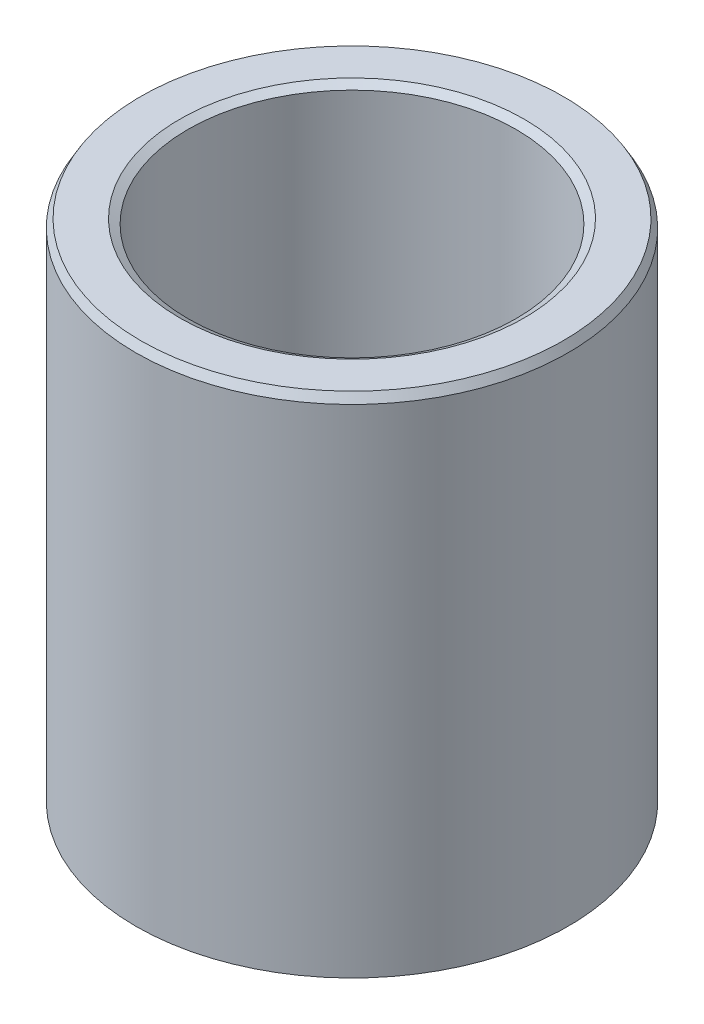
SolidWorks part; units mm, degrees
ref_plane "Front Plane" through (0, 0, 0) normal (0, 0, 1) x (1, 0, 0)
ref_plane "Top Plane" through (0, 0, 0) normal (0, 1, 0) x (1, 0, 0)
ref_plane "Right Plane" through (0, 0, 0) normal (1, 0, 0) x (0, 0, -1)
sketch "Sketch1" plane through (0, 0, 0) normal (0, 1, 0) x (1, 0, 0)
  circle A0 centre (0, 0) radius 22.5
  dimension "SLEEVE_OD" = 45
extrude "Boss-Extrude1" add sketch "Sketch1" along normal blind 53.0456
sketch "Sketch2" plane through (0, 0, 0) normal (0, 1, 0) x (1, 0, 0)
  circle A0 centre (0, 0) radius 17.0724
  dimension "BORE_D" = 34.1448
extrude "Cut-Extrude1" cut sketch "Sketch2" along normal through all
chamfer "Chamfer1" distance 0.8528 angle 30 4 edges at (0, 53.0456, 17.0724) (0, 0, 17.0724) (0, 0, 22.5) (0, 53.0456, 22.5) first distance on face at (0, 53.0456, 17.0724) first distance on face at (0, 0, 17.0724) first distance on face at (0, 53.0456, 22.5)
